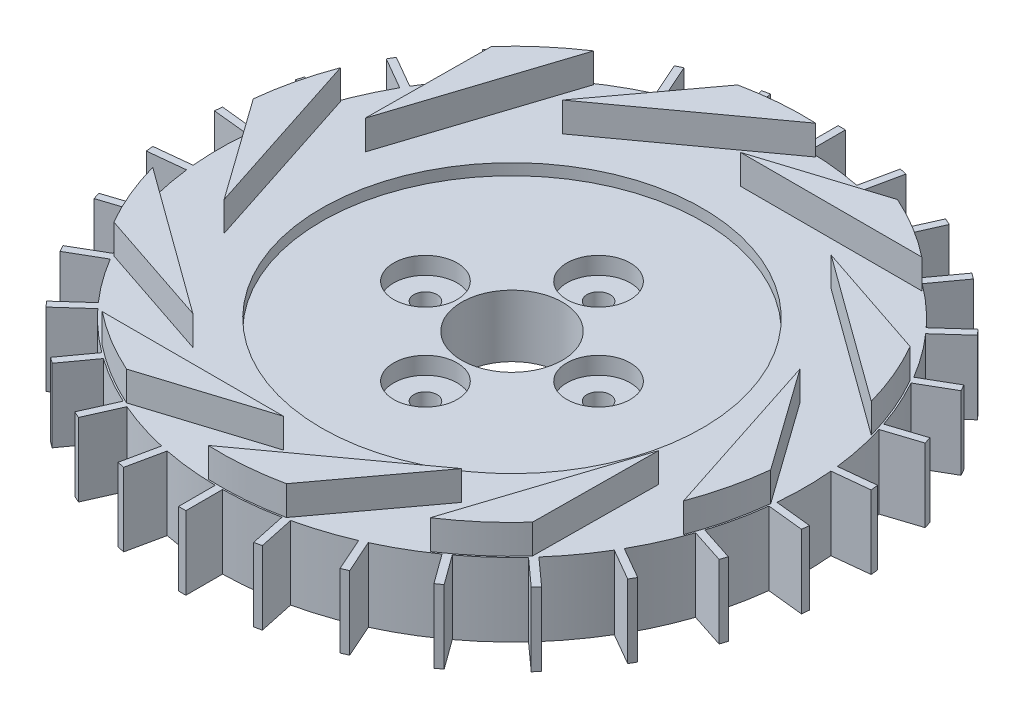
SolidWorks part; units mm, degrees
material "6061-T6 (SS)"
ref_plane "Front Plane" through (0, 0, 0) normal (0, 0, 1) x (1, 0, 0)
ref_plane "Top Plane" through (0, 0, 0) normal (0, 1, 0) x (1, 0, 0)
ref_plane "Right Plane" through (0, 0, 0) normal (1, 0, 0) x (0, 0, -1)
sketch "Sketch1" plane through (0, 0, 0) normal (1, 0, 0) x (0, 0, -1)
  line L0 (0, 26.2631) -> (0, -3.5886) construction
  line L1 (0, -3.5886) -> (-50.8, -3.5886)
  line L2 (-50.8, -3.5886) -> (-50.8, 9.1114)
  line L3 (-33.0001, 9.1114) -> (-50.8, 9.1114)
  line L4 (-33.0001, 9.1114) -> (-33.0001, 7.1515)
  line L5 (-33.0001, 7.1515) -> (0, 7.1515)
  line L6 (0, 7.1515) -> (0, -3.5886)
  dimension "D1" = 33.0001
  dimension "D2" = 50.8
  dimension "D3" = 1.96
  dimension "D4" = 12.7
revolve "Revolve1" add sketch "Sketch1" angle 360 about L0
sketch "Sketch2" plane through (0, 9.1114, 0) normal (0, 1, 0) x (1, 0, 0)
  line L8 (0, 39.6001) -> (19.9397, 39.6001) construction
  line L9 (0, 39.6001) -> (20.682, 46.1211)
  line L10 (0, 39.6001) -> (31.4123, 39.6001)
  arc A3 (20.682, 46.1211) -> (31.4123, 39.6001) centre (0, 0) cw
  circle A5 centre (0, 0) radius 33.0001 construction
  circle A7 centre (0, 0) radius 39.6001 construction
  point P9 (-2.4416, -40.4611)
  dimension "D1" = 66.0001
  dimension "D2" = 79.2001
  dimension "D4" = 50.546
  dimension "D3" = 17.5
extrude "Boss-Extrude1" add sketch "Sketch2" along normal blind 5.08
pattern_circular "CirPattern1" count 10 over 360 about axis through (0, 9.1114, 0) along (0, 1, 0) of "Boss-Extrude1"
ref_plane "Plane1" through (0, 0, 49.53) normal (0, 0, 1) x (1, 0, 0)
sketch "Sketch3" plane through (0, 0, 49.53) normal (0, 0, 1) x (1, 0, 0)
  line L0 (0, 0) -> (0, 9.7621) construction
  line L1 (0, -9.779) -> (0, 9.779) construction
  line L6 (-50.8, -3.5886) -> (50.8, -3.5886) construction
  line L13 (10.3772, 9.1114) -> (23.2763, 9.1114) construction
  line L14 (-0.635, -3.5886) -> (0.635, -3.5886)
  line L15 (-0.635, -3.5886) -> (-0.635, 9.1114)
  line L16 (-0.635, 9.1114) -> (0.635, 9.1114)
  line L17 (0.635, -3.5886) -> (0.635, 9.1114)
  point P11 (0, 9.1114)
  dimension "D1" = 1.27
extrude "Boss-Extrude2" add sketch "Sketch3" along normal blind 7.62 and the other way blind 0.254
pattern_circular "CirPattern16" count 30 over 360 of "Boss-Extrude2"
sketch "Sketch4" plane through (0, 7.1515, 0) normal (0, 1, 0) x (1, 0, 0)
  circle A0 centre (0, 0) radius 8.7312
  dimension "D1" = 17.4625
extrude "Cut-Extrude1" cut sketch "Sketch4" against normal up to next
sketch "Sketch5" plane through (0, -3.5886, 0) normal (0, -1, 0) x (-1, 0, 0)
  circle A0 centre (0, 0) radius 44.45
  dimension "D1" = 88.9
extrude "Cut-Extrude2" cut sketch "Sketch5" against normal blind 6.35
sketch "Sketch6" plane through (0, 2.7614, 0) normal (0, -1, 0) x (1, 0, 0)
  circle A0 centre (0, 0) radius 19.05
  circle A1 centre (0, 0) radius 8.7312 construction
  circle A2 centre (0, 0) radius 8.7312
  dimension "D1" = 38.1
extrude "Boss-Extrude3" add sketch "Sketch6" along normal up to surface (6.35 mm away)
sketch "Sketch9" plane through (0, 7.1515, 0) normal (0, 1, 0) x (1, 0, 0)
  circle A0 centre (0, 15) radius 2
  dimension "D1" = 4
  dimension "D2" = 15
extrude "Cut-Extrude3" cut sketch "Sketch9" against normal up to next
pattern_circular "CirPattern17" count 4 over 360 about axis through (0, 7.1515, 0) along (0, 1, 0) of "Cut-Extrude3"
ref_plane "Plane2" through (51.9838, 0, -23.1447) normal (-0.9135, 0, 0.4067) x (0.4067, 0, 0.9135)
sketch "Sketch10" plane through (51.9838, 0, -23.1447) normal (-0.9135, 0, 0.4067) x (0.4067, 0, 0.9135)
  line L0 (3.175, -3.5886) -> (3.175, -0.4136)
  line L1 (-46.1462, -3.5886) -> (-41.4681, -3.5886) construction
  line L2 (-3.175, -0.4136) -> (-3.175, -3.5886)
  line L3 (-3.175, -3.5886) -> (3.175, -3.5886)
  arc A0 (3.175, -0.4136) -> (-3.175, -0.4136) centre (0, -0.4136) ccw
  dimension "D1" = 3.175
  dimension "D2" = 3.175
sketch "Sketch11" plane through (0, 7.1515, 0) normal (0, 1, 0) x (1, 0, 0)
  circle A0 centre (0, -15) radius 5.5
  circle A1 centre (-15, 0) radius 5.5
  circle A2 centre (0, 15) radius 5.5
  circle A3 centre (15, 0) radius 5.5
  dimension "D1" = 11
extrude "Cut-Extrude5" cut sketch "Sketch11" against normal blind 3
ref_plane "Plane3" through (0, 16.7314, 0) normal (0, 1, 0) x (1, 0, 0)
ref_axis "Axis4" through (0, -3.5886, 0) along (0, 1, 0)
ref_point "Point1"
